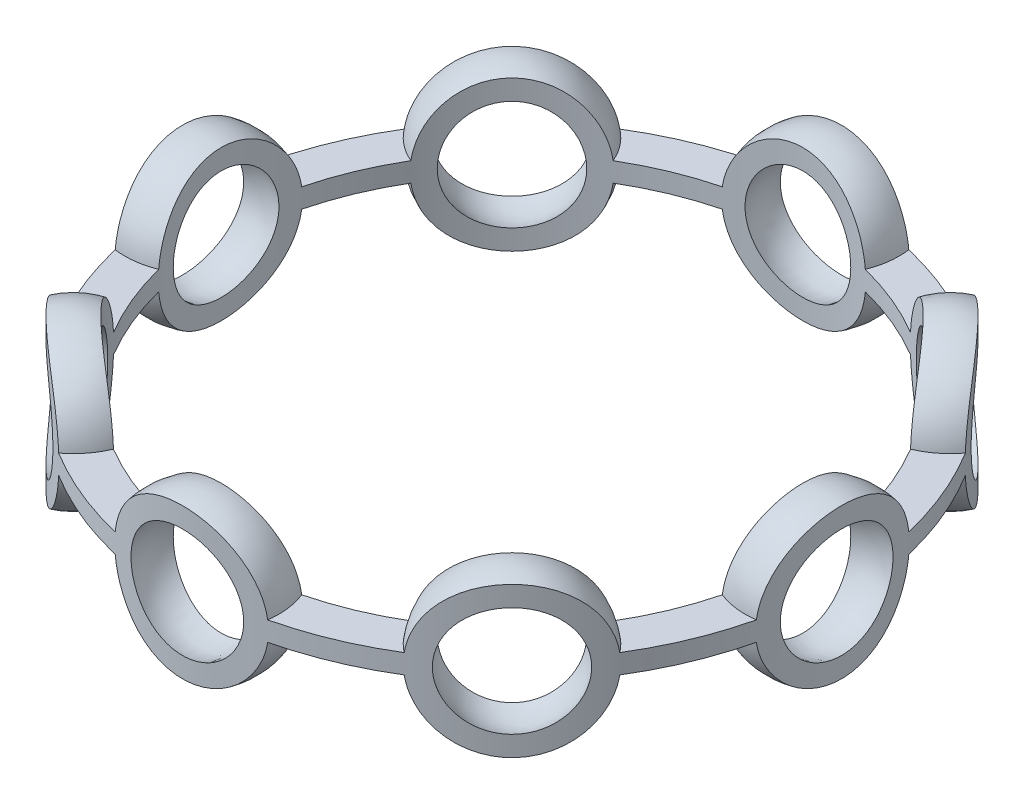
SolidWorks part; units mm, degrees
material "Chrome Stainless Steel"
ref_plane "Front Plane" through (0, 0, 0) normal (0, 0, 1) x (1, 0, 0)
ref_plane "Top Plane" through (0, 0, 0) normal (0, 1, 0) x (1, 0, 0)
ref_plane "Right Plane" through (0, 0, 0) normal (1, 0, 0) x (0, 0, -1)
sketch "Sketch3" plane through (0, 0, 0) normal (0, 0, 1) x (1, 0, 0)
  line L0 (0, 0) -> (0, 7.4846) construction
  line L1 (-17, -0.5) -> (-15, -0.5)
  line L2 (-17, -0.5) -> (-17, 0.5)
  line L3 (-17, 0.5) -> (-15, 0.5)
  line L4 (-15, -0.5) -> (-15, 0.5)
  line L5 (-17, -0.5) -> (-15, 0.5) construction
  line L6 (-17, 0.5) -> (-15, -0.5) construction
  point P0 (-16, 0)
  dimension "D1" = 16
  dimension "D2" = 2
  dimension "D3" = 1
revolve "Revolve1" add sketch "Sketch3" angle 360 about L0
sketch "Sketch4" plane through (0, 0, 0) normal (0, 1, 0) x (1, 0, 0)
  line L0 (-16, 4) -> (-16, -4)
  arc A0 (-16, 3) -> (-16, -3) centre (-16, 0) ccw
  arc A1 (-16, 4) -> (-16, -4) centre (-16, 0) ccw
  dimension "D2" = 1
  dimension "D3" = 6
  dimension "D1" = 16
revolve "Revolve2" add sketch "Sketch4" angle 360 about L0 region at (-16.0894, 0, -3.5)
revolve "Cut-Revolve1" cut sketch "Sketch4<5>" angle 360 about L0 region at (-17.2732, 0, 0)
sketch "Sketch4<5>" plane through (0, 0, 0) normal (0, 1, 0) x (1, 0, 0) same geometry as "Sketch4"
ref_axis "Axis1" through (0, 0.5, 0) along (0, -1, 0)
pattern_circular "CirPattern1" count 8 over 360 about axis through (0, 0.5, 0) along (0, -1, 0) of "Revolve2", "Cut-Revolve1"
sketch "Sketch6" plane through (0, 0, 0) normal (0, 1, 0) x (1, 0, 0)
  circle A0 centre (0, 0) radius 15
  circle A1 centre (0, 0) radius 20
  arc A2 (7.6715, 12.8899) -> (3.6899, 14.5391) centre (0, 0) ccw construction
  arc A3 (14.4927, 8.886) -> (8.886, 14.4927) centre (11.3137, 11.3137) ccw construction
  circle A4 centre (0, 0) radius 12
  circle A5 centre (0, 0) radius 17
  arc A6 (7.6443, 12.906) -> (12.906, 7.6443) centre (11.3137, 11.3137) ccw construction
  arc A7 (16.5391, 3.9318) -> (14.4751, 8.9146) centre (0, 0) ccw construction
extrude "Cut-Extrude3" cut sketch "Sketch6" against normal through all both and the other way through all contours A0 A4 | A1 A5 region at (-14.5757, 0, 0) region at (-19.4343, 0, 0)
